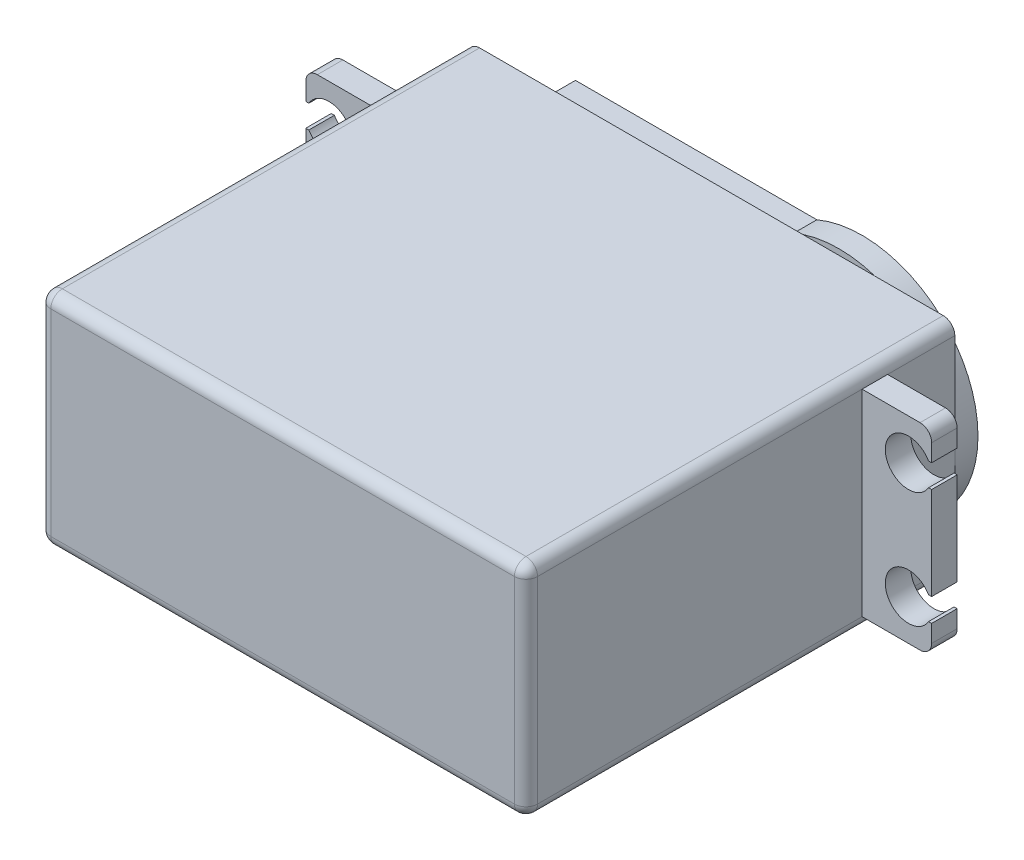
SolidWorks part; units mm, degrees
ref_plane "Front Plane" through (0, 0, 0) normal (0, 0, 1) x (1, 0, 0)
ref_plane "Top Plane" through (0, 0, 0) normal (0, 1, 0) x (1, 0, 0)
ref_plane "Right Plane" through (0, 0, 0) normal (1, 0, 0) x (0, 0, -1)
sketch "Sketch2" plane through (0, 0, 0) normal (0, 1, 0) x (1, 0, 0)
  line L1 (-31.0216, 21.9047) -> (10.9784, 21.9047)
  line L2 (-31.0216, 21.9047) -> (-31.0216, -15.0953)
  line L3 (-31.0216, -15.0953) -> (10.9784, -15.0953)
  line L4 (10.9784, 21.9047) -> (10.9784, -15.0953)
  dimension "D1" = 37
  dimension "D2" = 42
extrude "Boss-Extrude1" add sketch "Sketch2" along normal blind 19
fillet "Fillet1" radius 1 1 edges at (10.9784, 19, -3.4047)
fillet "Fillet2" radius 1 3 edges at (-31.0216, 19, -3.4047) (-31.0216, 0, -3.4047) (10.9784, 0, -3.4047)
sketch "Sketch3" plane through (10.9784, 0, 0) normal (1, 0, 0) x (0, 0, -1)
  line L0 (21.9047, 9.5) -> (13.9047, 9.5) construction
  line L1 (21.9047, 18) -> (21.9047, 1) construction
  line L2 (13.9047, 18) -> (13.9047, 1)
  line L3 (21.9047, 18) -> (-15.0953, 18) construction
  line L4 (-15.0953, 1) -> (21.9047, 1) construction
  line L5 (13.9047, 18) -> (16.1047, 18)
  line L6 (16.1047, 18) -> (16.1047, 1)
  line L7 (16.1047, 1) -> (13.9047, 1)
  line L8 (13.9047, 1) -> (13.9645, 0.9858)
  line M3 (-15.0953, 1) -> (21.9047, 1)
  line M5 (21.9047, 18) -> (-15.0953, 18)
  dimension "D1" = 8
  dimension "D2" = 2.2
extrude "Boss-Extrude2" add sketch "Sketch3" along normal blind 6 contours L6 L0 L2 M3 | L0 L6 L2 M5 region at (10.9784, 5.25, -15.0047) region at (10.9784, 13.75, -15.0047)
sketch "Sketch4" plane through (0, 0, -16.1047) normal (0, 0, -1) x (-1, 0, 0)
  line L0 (-16.9784, 9.5) -> (-10.9784, 9.5) construction
  line L1 (-16.9784, 18) -> (-16.9784, 1) construction
  line L2 (-10.9784, 18) -> (-10.9784, 1) construction
  line L4 (-16.9784, 9) -> (-10.9784, 9)
  line L5 (-16.9784, 9) -> (-16.9784, 10)
  line L6 (-16.9784, 10) -> (-10.9784, 10)
  line L7 (-10.9784, 9) -> (-10.9784, 10)
  line L8 (-16.9784, 9) -> (-10.9784, 10) construction
  line L9 (-16.9784, 10) -> (-10.9784, 9) construction
  point P6 (-13.9784, 9.5)
  dimension "D1" = 1
extrude "Boss-Extrude3" add sketch "Sketch4" along normal blind 1
chamfer "Chamfer1" distance 1 distance2 6 1 edges at (16.9784, 9.5, -17.1047) first distance on face at (16.9784, 9.5, -15.8047)
fillet "Fillet3" radius 1 2 edges at (16.9784, 18, -15.0047) (16.9784, 1, -15.0047)
sketch "Sketch5" plane through (0, 0, -16.1047) normal (0, 0, -1) x (-1, 0, 0)
  line L0 (-10.9784, 18) -> (-14.9784, 18) construction
  line L1 (-15.9784, 1) -> (-10.9784, 1) construction
  line L2 (-15.9784, 18) -> (-10.9784, 18) construction
  line L4 (-14.9784, 14.5) -> (-14.9784, 4.5) construction
  line L6 (-14.9784, 14.5) -> (-16.9784, 14.5) construction
  line L7 (-16.9784, 17) -> (-16.9784, 10) construction
  line L8 (-14.9784, 4.5) -> (-16.988, 4.5) construction
  line L9 (-16.9784, 15.5) -> (-16.9784, 13.5)
  line L10 (-16.9784, 3.5) -> (-16.9784, 5.5)
  line L11 (-16.9784, 15.5) -> (-16.7104, 15.5)
  line L12 (-16.9784, 3.5) -> (-16.7104, 3.5)
  line L13 (-16.9784, 13.5) -> (-16.7104, 13.5)
  line L14 (-16.9784, 5.5) -> (-16.7104, 5.5)
  arc A0 (-16.7104, 13.5) -> (-16.7104, 15.5) centre (-14.9784, 14.5) ccw
  arc A1 (-16.7104, 3.5) -> (-16.7104, 5.5) centre (-14.9784, 4.5) ccw
  point P22 (-16.9784, 14.5)
  dimension "D2" = 4
  dimension "D3" = 4
  dimension "D1" = 10
  dimension "D4" = 2
  dimension "D5" = 3.5
  dimension "D6" = 3.5
  dimension "D7" = 2
  dimension "D8" = 2
  dimension "D9" = 10
extrude "Cut-Extrude1" cut sketch "Sketch5" against normal blind 6
ref_plane "Plane5" through (-10.0216, 0, 0) normal (1, 0, 0) x (0, 0, -1)
mirror "Mirror9" about plane through (-10.0216, 0, 0) normal (1, 0, 0) of "Cut-Extrude1", "Fillet3", "Boss-Extrude3", "Boss-Extrude2"
chamfer "Chamfer2" distance 6 distance2 1 1 edges at (-37.0216, 9.5, -17.1047) first distance on face at (-34.0216, 9.5, -17.1047)
fillet "Fillet4" radius 1 8 edges at (-30.7287, 18.7071, 15.0953) (-31.0216, 9.5, 15.0953) (-30.7287, 0.2929, 15.0953) (-10.0216, 0, 15.0953) (10.6855, 0.2929, 15.0953) (10.9784, 9.5, 15.0953) (10.6855, 18.7071, 15.0953) (-10.0216, 19, 15.0953)
sketch "Sketch8" plane through (0, 0, -21.9047) normal (0, 0, -1) x (-1, 0, 0)
  line L0 (-10.9784, 9.5) -> (-0.9784, 9.5) construction
  line L1 (-10.9784, 9) -> (-10.9784, 10) construction
  line L2 (2.9241, 18.7071) -> (23.753, 18.7071)
  line L3 (2.9241, 0.2929) -> (23.753, 0.2929)
  line L4 (23.753, 18.7071) -> (23.753, 14.0234)
  line L5 (23.753, 4.9766) -> (23.753, 0.2929)
  arc A0 (2.9241, 18.7071) -> (2.9241, 0.2929) centre (-0.9784, 9.5) ccw
  arc A1 (23.753, 4.9766) -> (23.753, 14.0234) centre (19.8359, 9.5) ccw
  dimension "D2" = 20
  dimension "D1" = 10
extrude "Boss-Extrude4" add sketch "Sketch8" along normal blind 2
sketch "Sketch9" plane through (0, 0, -23.9047) normal (0, 0, -1) x (-1, 0, 0)
  circle A0 centre (-0.9784, 9.5) radius 6.5744
extrude "Boss-Extrude5" add sketch "Sketch9" along normal blind 1
sketch "Sketch10" plane through (0, 0, -24.9047) normal (0, 0, -1) x (-1, 0, 0)
  circle A0 centre (-0.9784, 9.5) radius 5.6897
extrude "Boss-Extrude6" add sketch "Sketch10" along normal blind 0.7
sketch "Sketch11" plane through (0, 0, -25.6047) normal (0, 0, -1) x (-1, 0, 0)
  circle A0 centre (-0.9784, 9.5) radius 1.55
  circle A1 centre (-0.9784, 9.5) radius 5.6897 construction
  dimension "D1" = 3.1
extrude "Cut-Extrude2" cut sketch "Sketch11" against normal blind 10 contours A0
